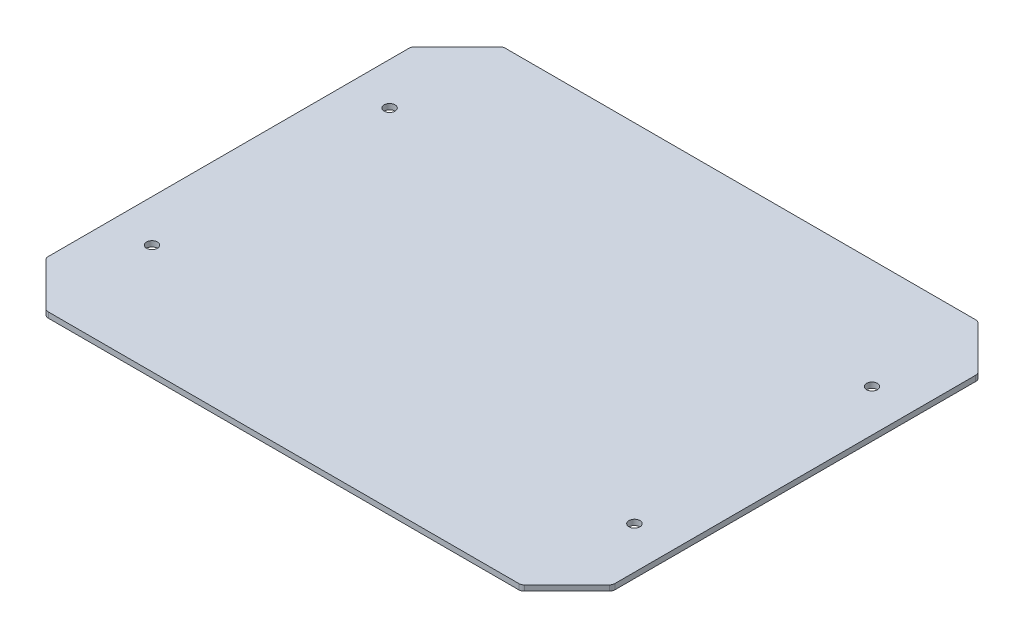
SolidWorks part; units mm, degrees
ref_plane "Plan de face" through (0, 0, 0) normal (0, 0, 1) x (1, 0, 0)
ref_plane "Plan de dessus" through (0, 0, 0) normal (0, 1, 0) x (1, 0, 0)
ref_plane "Plan de droite" through (0, 0, 0) normal (1, 0, 0) x (0, 0, -1)
sketch "Esquisse1" plane through (0, 0, 0) normal (0, 1, 0) x (1, 0, 0)
  line L0 (0, 125) -> (0, -125) construction
  line L1 (-155, 0) -> (155, 0) construction
  line L2 (-130, 125) -> (130, 125)
  line L3 (-130, -125) -> (130, -125)
  line L4 (-155, 100) -> (-155, -100)
  line L5 (155, 100) -> (155, -100)
  line L6 (-155, 100) -> (-130, 125)
  line L7 (-155, -100) -> (-130, -125)
  line L8 (130, -125) -> (155, -100)
  line L9 (130, 125) -> (155, 100)
  point P3 (0, 0)
  point P6 (0, 0)
  point P8 (0, 125)
  point P11 (0, -125)
  point P14 (-155, 0)
  point P17 (155, 0)
  dimension "D1" = 310
  dimension "D2" = 250
  dimension "D3" = 135
  dimension "D4" = 260
  dimension "D5" = 200
extrude "Boss.-Extru.1" add sketch "Esquisse1" along normal blind 3
fillet "Congé1" radius 3 8 edges at (-130, 1.5, 125) (-155, 1.5, 100) (130, 1.5, 125) (155, 1.5, 100) (155, 1.5, -100) (130, 1.5, -125) (-130, 1.5, -125) (-155, 1.5, -100)
sketch "Esquisse2" plane through (0, 3, 0) normal (0, 1, 0) x (1, 0, 0)
  line L0 (0, 125) -> (0, -125) construction
  line L1 (128.7574, 125) -> (-128.7574, 125) construction
  line L2 (-128.7574, -125) -> (128.7574, -125) construction
  line L3 (-155, 0) -> (155, 0) construction
  line L4 (-155, 98.7574) -> (-155, -98.7574) construction
  line L5 (155, -98.7574) -> (155, 98.7574) construction
  line L6 (-132, 65) -> (-132, 0) construction
  line L7 (-132, 65) -> (-155, 65) construction
  circle A0 centre (-132, 65) radius 3
  circle A1 centre (-132, -65) radius 3
  circle A2 centre (132, -65) radius 3
  circle A3 centre (132, 65) radius 3
  dimension "D1" = 6
  dimension "D2" = 23
  dimension "D3" = 65
extrude "Perçage Profilé" cut sketch "Esquisse2" against normal through all
